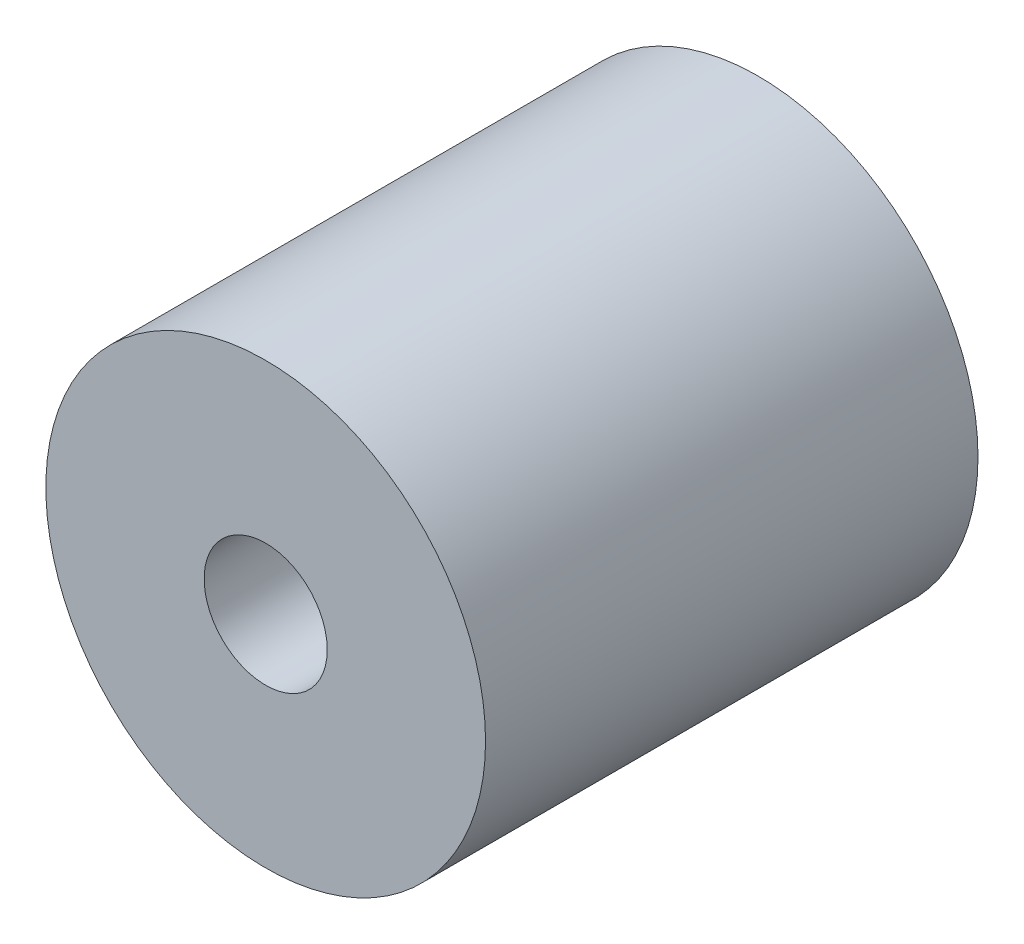
SolidWorks part; units mm, degrees
ref_plane "Front Plane" through (0, 0, 0) normal (0, 0, 1) x (1, 0, 0)
ref_plane "Top Plane" through (0, 0, 0) normal (0, 1, 0) x (1, 0, 0)
ref_plane "Right Plane" through (0, 0, 0) normal (1, 0, 0) x (0, 0, -1)
sketch "Sketch2" plane through (0, 0, 0) normal (0, 0, 1) x (1, 0, 0)
  circle A0 centre (0, 0) radius 6.25
  dimension "D1" = 12.5
extrude "Boss-Extrude1" add sketch "Sketch2" along normal blind 14 contours A0
sketch "Sketch4" plane through (0, 0, 14) normal (0, 0, 1) x (1, 0, 0)
  circle A0 centre (0, 0) radius 3.375
  circle A1 centre (0, 0) radius 1.75
  dimension "D1" = 6.75
  dimension "D2" = 3.5
extrude "Cut-Extrude1" cut sketch "Sketch4" against normal blind 5.5 contours A1 region at (0, 0, 14)
extrude "Cut-Extrude2" cut sketch "Sketch4<3>" along normal blind 5.5 from surface contours A0 starting at face at (6.25, 0, 0)
sketch "Sketch4<3>" plane through (0, 0, 14) normal (0, 0, 1) x (1, 0, 0) same geometry as "Sketch4"
